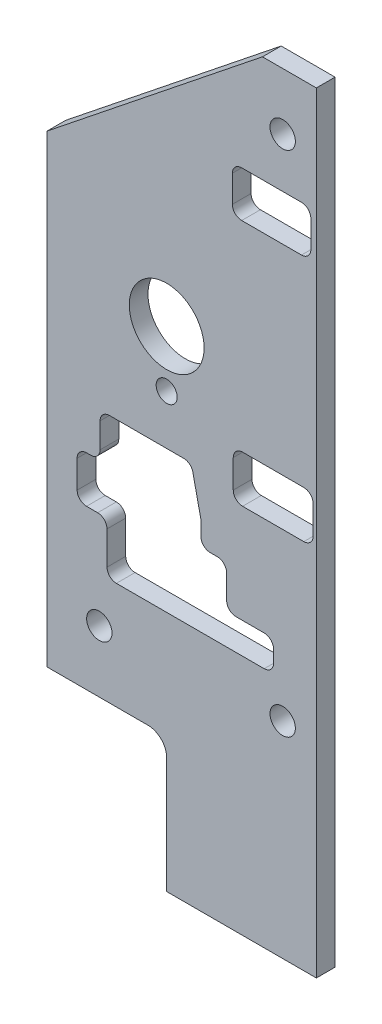
SolidWorks part; units mm, degrees
material "ABS PC"
ref_plane "Front Plane" through (0, 0, 0) normal (0, 0, 1) x (1, 0, 0)
ref_plane "Top Plane" through (0, 0, 0) normal (0, 1, 0) x (1, 0, 0)
ref_plane "Right Plane" through (0, 0, 0) normal (1, 0, 0) x (0, 0, -1)
sketch "Sketch1" plane through (0, 0, 0) normal (0, 0, 1) x (1, 0, 0)
  line L7 (-25.4, 0) -> (0, 0)
  line L8 (0, 0) -> (0, 130.81)
  line L9 (0, 130.81) -> (-9.144, 130.81)
  line L10 (-9.144, 130.81) -> (-45.72, 101.6)
  line L11 (-45.72, 101.6) -> (-45.72, 22.86)
  line L12 (-45.72, 22.86) -> (-28.575, 22.86)
  line L13 (-25.4, 19.685) -> (-25.4, 0)
  line L14 (-25.4, 0) -> (0, 0)
  line L15 (0, 0) -> (0, 130.81)
  line L16 (0, 130.81) -> (-9.144, 130.81)
  line L17 (-9.144, 130.81) -> (-45.72, 101.6)
  line L18 (-45.72, 101.6) -> (-45.72, 22.86)
  line L19 (-45.72, 22.86) -> (-28.575, 22.86)
  line L20 (-25.4, 19.685) -> (-25.4, 0)
  arc A1 (-25.4, 19.685) -> (-28.575, 22.86) centre (-28.575, 19.685) ccw
  arc A2 (-25.4, 19.685) -> (-28.575, 22.86) centre (-28.575, 19.685) ccw
  dimension "D1" = 0
extrude "Boss-Extrude1" add sketch "Sketch1" against normal blind 3.175
hole_wizard "#6 Clearance Hole1" positions "Sketch3" profile "Sketch2" hole size "#6" standard "ANSI Inch" end condition through all
sketch "Sketch3" plane through (0, 0, 0) normal (0, 0, 1) x (1, 0, 0)
  point P0 (-5.715, 34.925)
  point P3 (-36.83, 33.3375)
  point P6 (-5.715, 121.158)
sketch "Sketch2" plane through (-5.715, 34.925, 0) normal (1, 0, 0) x (0, -1, 0)
  line L0 (0, 0) -> (0, 3.175)
  line L1 (0, 3.175) -> (2.1526, 3.175)
  line L2 (2.1526, 3.175) -> (2.1526, 0)
  line L5 (2.1526, 0) -> (0, 0)
  line L11 (0, -6.35) -> (0, 107.95) construction
  dimension "Thru Hole Dia." = 4.3053
  dimension "Thru Hole Depth" = 3.175
hole_wizard "1/2 (0.5) Diameter Hole1" positions "Sketch5" profile "Sketch4" hole size "1/2" standard "ANSI Inch" end condition through all
sketch "Sketch5" plane through (0, 0, 0) normal (0, 0, 1) x (1, 0, 0)
  point P0 (-25.4, 83.058)
sketch "Sketch4" plane through (-25.4, 83.058, 0) normal (1, 0, 0) x (0, -1, 0)
  line L0 (0, 0) -> (0, 3.175)
  line L1 (0, 3.175) -> (6.35, 3.175)
  line L2 (6.35, 3.175) -> (6.35, 0)
  line L5 (6.35, 0) -> (0, 0)
  line L11 (0, -6.35) -> (0, 107.95) construction
  dimension "Thru Hole Dia." = 12.7
  dimension "Thru Hole Depth" = 3.175
hole_wizard "9/64 (0.14063) Diameter Hole1" positions "Sketch7" profile "Sketch6" hole size "9/64" standard "ANSI Inch" end condition through all
sketch "Sketch7" plane through (0, 0, 0) normal (0, 0, 1) x (1, 0, 0)
  point P0 (-25.4, 73.533)
sketch "Sketch6" plane through (-25.4, 73.533, 0) normal (1, 0, 0) x (0, -1, 0)
  line L0 (0, 0) -> (0, 3.175)
  line L1 (0, 3.175) -> (1.786, 3.175)
  line L2 (1.786, 3.175) -> (1.786, 0)
  line L5 (1.786, 0) -> (0, 0)
  line L11 (0, -6.35) -> (0, 107.95) construction
  dimension "Thru Hole Dia." = 3.572
  dimension "Thru Hole Depth" = 3.175
sketch "Sketch8" plane through (0, 0, 0) normal (0, 0, 1) x (1, 0, 0)
  line L0 (-40.594, 56.097) -> (-40.594, 51.4082)
  line L1 (-12.6694, 112.7343) -> (-2.5255, 112.7343)
  line L2 (-14.2569, 111.1468) -> (-14.2569, 106.5774)
  line L3 (-12.6694, 104.9899) -> (-2.5255, 104.9899)
  line L4 (-0.938, 111.1468) -> (-0.938, 106.5774)
  line L5 (-12.5166, 71.0257) -> (-2.1292, 71.0257)
  line L6 (-14.1041, 69.4382) -> (-14.1041, 64.6553)
  line L7 (-12.5166, 63.0678) -> (-2.1292, 63.0678)
  line L8 (-0.5417, 69.4382) -> (-0.5417, 64.6553)
  line L9 (-39.0065, 49.8207) -> (-37.1138, 49.8207)
  line L10 (-35.5263, 48.2332) -> (-35.5263, 42.6198)
  line L11 (-33.9388, 41.0323) -> (-8.8474, 41.0323)
  line L16 (-15.2263, 47.8662) -> (-15.2263, 51.9267)
  line L17 (-16.8138, 53.5142) -> (-18.0162, 53.5142)
  line L18 (-19.6037, 55.1017) -> (-19.6037, 57.4807)
  line L21 (-22.5115, 65.1151) -> (-35.1151, 65.1151)
  line L22 (-36.7026, 63.5276) -> (-36.7026, 59.272)
  line L23 (-38.2901, 57.6845) -> (-39.0065, 57.6845)
  line L24 (-20.9605, 63.8662) -> (-19.6402, 57.8193)
  line L25 (-13.6388, 46.2787) -> (-8.8474, 46.2787)
  line L26 (-7.2599, 44.6912) -> (-7.2599, 42.6198)
  arc A0 (-2.5255, 112.7343) -> (-0.938, 111.1468) centre (-2.5255, 111.1468) cw
  arc A1 (-2.5255, 104.9899) -> (-0.938, 106.5774) centre (-2.5255, 106.5774) ccw
  arc A2 (-14.2569, 106.5774) -> (-12.6694, 104.9899) centre (-12.6694, 106.5774) ccw
  arc A3 (-12.6694, 112.7343) -> (-14.2569, 111.1468) centre (-12.6694, 111.1468) ccw
  arc A4 (-2.1292, 71.0257) -> (-0.5417, 69.4382) centre (-2.1292, 69.4382) cw
  arc A5 (-2.1292, 63.0678) -> (-0.5417, 64.6553) centre (-2.1292, 64.6553) ccw
  arc A6 (-14.1041, 64.6553) -> (-12.5166, 63.0678) centre (-12.5166, 64.6553) ccw
  arc A7 (-12.5166, 71.0257) -> (-14.1041, 69.4382) centre (-12.5166, 69.4382) ccw
  arc A8 (-35.1151, 65.1151) -> (-36.7026, 63.5276) centre (-35.1151, 63.5276) ccw
  arc A9 (-20.9605, 63.8662) -> (-22.5115, 65.1151) centre (-22.5115, 63.5276) ccw
  arc A10 (-19.6037, 57.4807) -> (-19.6402, 57.8193) centre (-21.1912, 57.4807) ccw
  arc A11 (-18.0162, 53.5142) -> (-19.6037, 55.1017) centre (-18.0162, 55.1017) cw
  arc A12 (-15.2263, 51.9267) -> (-16.8138, 53.5142) centre (-16.8138, 51.9267) ccw
  arc A13 (-13.6388, 46.2787) -> (-15.2263, 47.8662) centre (-13.6388, 47.8662) cw
  arc A14 (-8.8474, 46.2787) -> (-7.2599, 44.6912) centre (-8.8474, 44.6912) cw
  arc A15 (-7.2599, 42.6198) -> (-8.8474, 41.0323) centre (-8.8474, 42.6198) cw
  arc A16 (-35.5263, 42.6198) -> (-33.9388, 41.0323) centre (-33.9388, 42.6198) ccw
  arc A17 (-37.1138, 49.8207) -> (-35.5263, 48.2332) centre (-37.1138, 48.2332) cw
  arc A18 (-40.594, 51.4082) -> (-39.0065, 49.8207) centre (-39.0065, 51.4082) ccw
  arc A19 (-39.0065, 57.6845) -> (-40.594, 56.097) centre (-39.0065, 56.097) ccw
  arc A20 (-36.7026, 59.272) -> (-38.2901, 57.6845) centre (-38.2901, 59.272) cw
  point P4 (-6.9956, 40.2996)
  dimension "D1" = 1.5875
extrude "Cut-Extrude1" cut sketch "Sketch8" against normal through all
